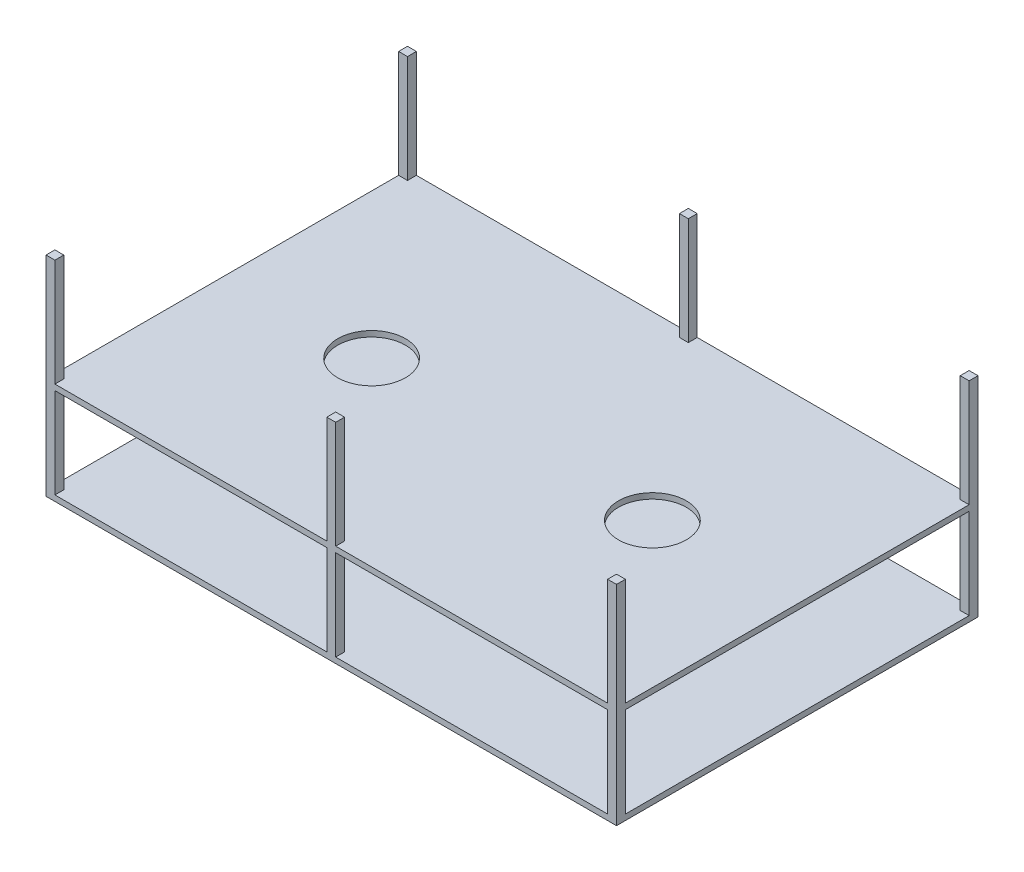
SolidWorks part; units mm, degrees
ref_plane "Front Plane" through (0, 0, 0) normal (0, 0, 1) x (1, 0, 0)
ref_plane "Top Plane" through (0, 0, 0) normal (0, 1, 0) x (1, 0, 0)
ref_plane "Right Plane" through (0, 0, 0) normal (1, 0, 0) x (0, 0, -1)
sketch "Sketch1" plane through (0, 2661.4582, 0) normal (0, -1, 0) x (1, 0, 0)
  line L0 (-9.2336, 757.9374) -> (-9.2336, -1003.3547) construction
  line L1 (-1228.4336, 757.9374) -> (1209.9664, 757.9374) construction
  line L2 (-1228.4336, 8.6374) -> (529.5248, 8.6374) construction
  line L3 (-1228.4336, -740.6626) -> (-1228.4336, 757.9374) construction
  line L4 (1233.4664, 781.4374) -> (1273.4664, 781.4374)
  line L5 (-1251.9336, 781.4374) -> (-1291.9336, 781.4374)
  line L6 (-1251.9336, 781.4374) -> (-1251.9336, 821.4374)
  line L7 (-1251.9336, 821.4374) -> (-1291.9336, 821.4374)
  line L8 (-1291.9336, 781.4374) -> (-1291.9336, 821.4374)
  line L9 (-29.2336, 821.4374) -> (10.7664, 821.4374)
  line L10 (-29.2336, 821.4374) -> (-29.2336, 781.4374)
  line L11 (-29.2336, 781.4374) -> (10.7664, 781.4374)
  line L12 (10.7664, 821.4374) -> (10.7664, 781.4374)
  line L13 (1233.4664, 781.4374) -> (1233.4664, 821.4374)
  line L14 (1233.4664, 821.4374) -> (1273.4664, 821.4374)
  line L15 (1273.4664, 781.4374) -> (1273.4664, 821.4374)
  line L16 (-1251.9336, -764.1626) -> (-1291.9336, -764.1626)
  line L17 (-1251.9336, -764.1626) -> (-1251.9336, -804.1626)
  line L18 (-1251.9336, -804.1626) -> (-1291.9336, -804.1626)
  line L19 (-1291.9336, -764.1626) -> (-1291.9336, -804.1626)
  line L20 (-29.2336, -764.1626) -> (10.7664, -764.1626)
  line L21 (10.7664, -804.1626) -> (10.7664, -764.1626)
  line L22 (-29.2336, -804.1626) -> (10.7664, -804.1626)
  line L23 (-29.2336, -804.1626) -> (-29.2336, -764.1626)
  line L24 (1233.4664, -764.1626) -> (1273.4664, -764.1626)
  line L25 (1273.4664, -764.1626) -> (1273.4664, -804.1626)
  line L26 (1233.4664, -804.1626) -> (1273.4664, -804.1626)
  line L27 (1233.4664, -764.1626) -> (1233.4664, -804.1626)
  point P16 (-9.2336, 781.4374)
  dimension "D1" = 40
  dimension "D2" = 40
  dimension "D3" = 63.5
  dimension "D4" = 63.5
extrude "Boss-Extrude1" add sketch "Sketch1" along normal blind 939.8
sketch "Sketch2" plane through (0, 1721.6582, 0) normal (0, -1, 0) x (1, 0, 0)
  line L1 (-1291.9336, 821.4374) -> (1273.4664, 821.4374)
  line L2 (-1291.9336, 821.4374) -> (-1291.9336, -804.1626)
  line L3 (-1291.9336, -804.1626) -> (1273.4664, -804.1626)
  line L4 (1273.4664, 821.4374) -> (1273.4664, -804.1626)
extrude "Boss-Extrude2" add sketch "Sketch2" against normal blind 25.4
ref_plane "Plane1" through (0, 2153.4582, 0) normal (0, -1, 0) x (1, 0, 0)
sketch "Sketch3" plane through (0, 2153.4582, 0) normal (0, -1, 0) x (1, 0, 0)
  line L1 (-1291.9336, 821.4374) -> (1273.4664, 821.4374)
  line L2 (-1291.9336, 821.4374) -> (-1291.9336, -804.1626)
  line L3 (-1291.9336, -804.1626) -> (1273.4664, -804.1626)
  line L4 (1273.4664, 821.4374) -> (1273.4664, -804.1626)
extrude "Boss-Extrude3" add sketch "Sketch3" against normal blind 25.4
sketch "Sketch4" plane through (0, 2178.8582, 0) normal (0, 1, 0) x (1, 0, 0)
  line L0 (-1251.9336, 764.1626) -> (-29.2336, -781.4374) construction
  line L1 (-29.2336, 764.1626) -> (-1251.9336, -781.4374) construction
  line L2 (10.7664, 764.1626) -> (1233.4664, -781.4374) construction
  line L3 (1233.4664, 764.1626) -> (10.7664, -781.4374) construction
  circle A0 centre (-640.5836, -8.6374) radius 152.4
  circle A1 centre (622.1164, -8.6374) radius 152.4
  dimension "D1" = 304.8
extrude "Cut-Extrude1" cut sketch "Sketch4" against normal through all
